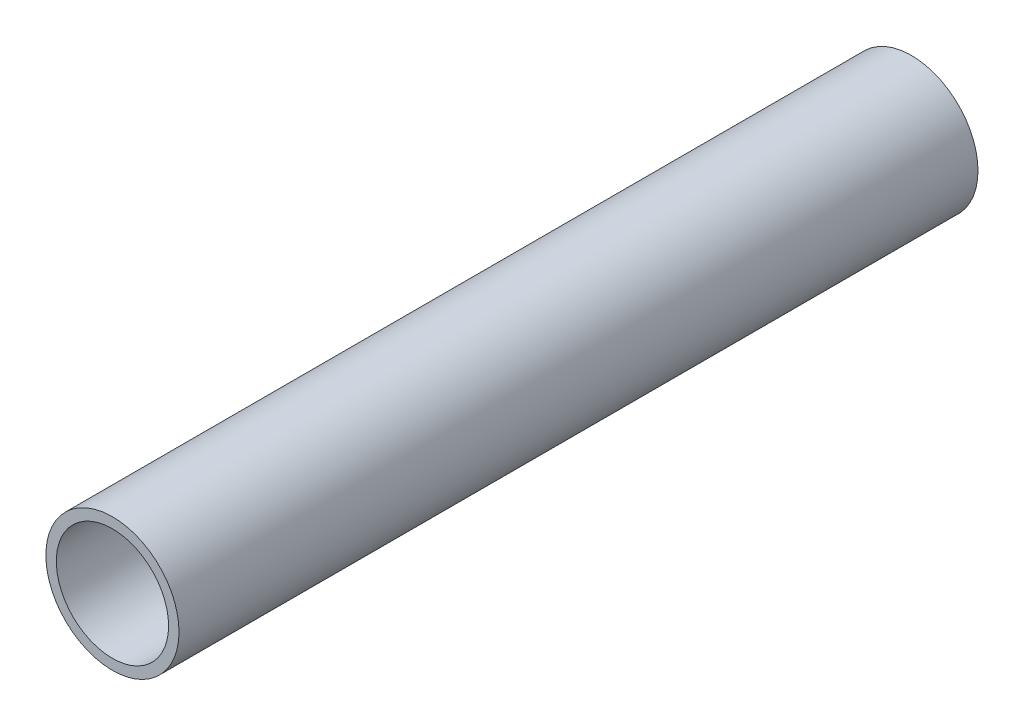
SolidWorks part; units mm, degrees
ref_plane "Front Plane" through (0, 0, 0) normal (0, 0, 1) x (1, 0, 0)
ref_plane "Top Plane" through (0, 0, 0) normal (0, 1, 0) x (1, 0, 0)
ref_plane "Right Plane" through (0, 0, 0) normal (1, 0, 0) x (0, 0, -1)
sketch "Sketch1" plane through (0, 0, 0) normal (0, 0, 1) x (1, 0, 0)
  line L0 (-7.9375, 0) -> (7.9375, 0) construction
  line L1 (0, -7.9375) -> (0, 7.9375) construction
  circle A0 centre (0, 0) radius 7.9375
  circle A1 centre (0, 0) radius 6.6929
  point P4 (0, 0)
  point P9 (0, 0)
  point P10 (6.6929, 0)
  dimension "ID" = 13.3858
  dimension "OD" = 15.875
  dimension "Wall Thickness" = 1.2446
sketch "Sketch2" plane through (0, 0, 0) normal (1, 0, 0) x (0, 0, -1)
  line L0 (47.6346, 7.9375) -> (-47.6346, 7.9375) construction
  line L1 (0, 7.9375) -> (0, -7.9375) construction
  point P3 (-29.3783, 7.9375)
  point P4 (0, 7.9375)
  point P5 (29.3783, 7.9375)
  dimension "Length" = 95.2692
  dimension "D1" = 18.2563
  dimension "D2" = 18.2562
sketch "Sketch3" plane through (0, 0, 0) normal (0, 0, 1) x (1, 0, 0)
  line L0 (0, -7.9375) -> (0, 7.9375) construction
  circle A0 centre (0, 0) radius 7.9375
  circle A1 centre (0, 0) radius 6.6929
  circle A2 centre (0, 0) radius 6.6929 construction
extrude "Boss-Extrude1" add sketch "Sketch3" along normal mid plane 95.2692
equation "\"D1@Boss-Extrude1\" = \"Length@Sketch2\""
equation "\"D1@Sketch2\"=\"OD@Sketch1\"*1.15"
equation "\"D2@Sketch2\"=\"D1@Sketch2\""
